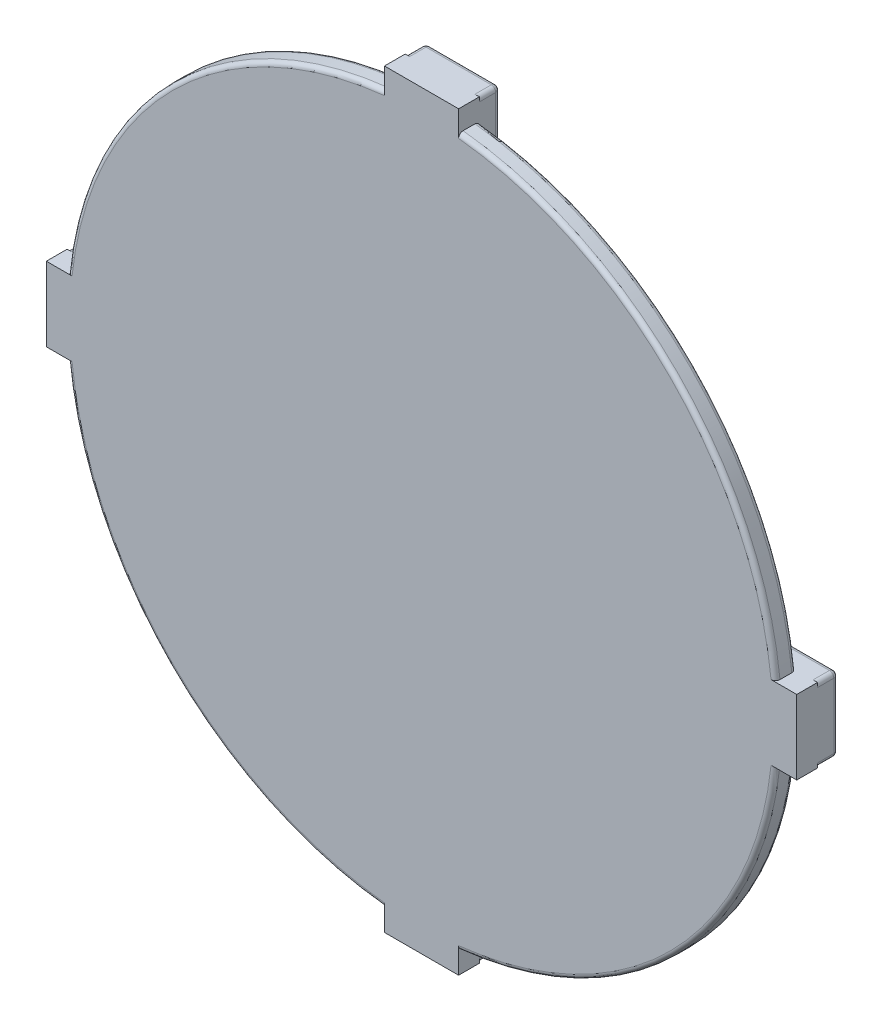
SolidWorks part; units mm, degrees
ref_plane "Front" through (0, 0, 0) normal (0, 0, 1) x (1, 0, 0)
ref_plane "Top" through (0, 0, 0) normal (0, 1, 0) x (1, 0, 0)
ref_plane "Right" through (0, 0, 0) normal (1, 0, 0) x (0, 0, -1)
sketch "Sketch2" plane through (0, 0, 0) normal (0, 0, 1) x (1, 0, 0)
  circle A0 centre (0, 0) radius 60.96
  dimension "D1" = 121.92
extrude "Boss-Extrude1" add sketch "Sketch2" along normal blind 3.556
fillet "Fillet1" radius 0.762 2 edges at (60.96, 0, 0) (60.96, 0, 3.556)
sketch "Sketch3" plane through (0, 0, 0) normal (0, 0, 1) x (1, 0, 0)
  line L0 (-90.3354, 0) -> (94.7496, 0) construction
  line L1 (0, -87.0909) -> (0, 87.4293) construction
  line L2 (64.262, -6.35) -> (-64.262, -6.35)
  line L3 (-64.262, -6.35) -> (-64.262, 6.35)
  line L4 (64.262, -6.35) -> (64.262, 6.35)
  line L5 (64.262, 6.35) -> (-64.262, 6.35)
  point P8 (0, -6.35)
  point P11 (64.262, 0)
  point P12 (-64.262, 0)
  dimension "D1" = 6.35
  dimension "D2" = 64.262
extrude "Boss-Extrude2" add sketch "Sketch3" against normal blind 3.556
sketch "Sketch4" plane through (0, 0, 0) normal (0, 0, 1) x (1, 0, 0)
  line L0 (0, 77.441) -> (0, -78.3479) construction
  line L1 (-6.35, -64.262) -> (-6.35, 64.262)
  line L2 (-6.35, 64.262) -> (6.35, 64.262)
  line L3 (-72.9977, 0) -> (84.2421, 0) construction
  line L4 (-6.35, -64.262) -> (6.35, -64.262)
  line L5 (6.35, -64.262) -> (6.35, 64.262)
  point P10 (-6.35, 0)
  point P11 (0, -64.262)
  point P12 (0, 64.262)
  dimension "D1" = 64.262
  dimension "D2" = 6.35
extrude "Boss-Extrude3" add sketch "Sketch4" against normal blind 3.556
fillet "Fillet2" radius 0.762 20 edges at (-64.262, 0, -3.556) (-35.306, -6.35, -3.556) (-6.35, -35.306, -3.556) (0, -64.262, -3.556) (6.35, -35.306, -3.556) (35.306, -6.35, -3.556) (64.262, 0, -3.556) (35.306, 6.35, -3.556) (6.35, 35.306, -3.556) (0, 64.262, -3.556) (-6.35, 35.306, -3.556) (-35.306, 6.35, -3.556) (-64.262, 6.35, -1.778) (-64.262, -6.35, -1.778) (-6.35, -64.262, -1.778) (6.35, -64.262, -1.778) (64.262, -6.35, -1.778) (64.262, 6.35, -1.778) (-6.35, 64.262, -1.778) (6.35, 64.262, -1.778)
extrude "Boss-Extrude4" add sketch "Sketch3<2>" along normal up to surface (3.556 mm away) up to face at (60.198, 0, 3.556)
sketch "Sketch3<2>" plane through (0, 0, 0) normal (0, 0, 1) x (1, 0, 0) same geometry as "Sketch3"
extrude "Boss-Extrude5" add sketch "Sketch4<2>" along normal up to surface (3.556 mm away) up to face at (0, 0, 3.556)
sketch "Sketch4<2>" plane through (0, 0, 0) normal (0, 0, 1) x (1, 0, 0) same geometry as "Sketch4"
